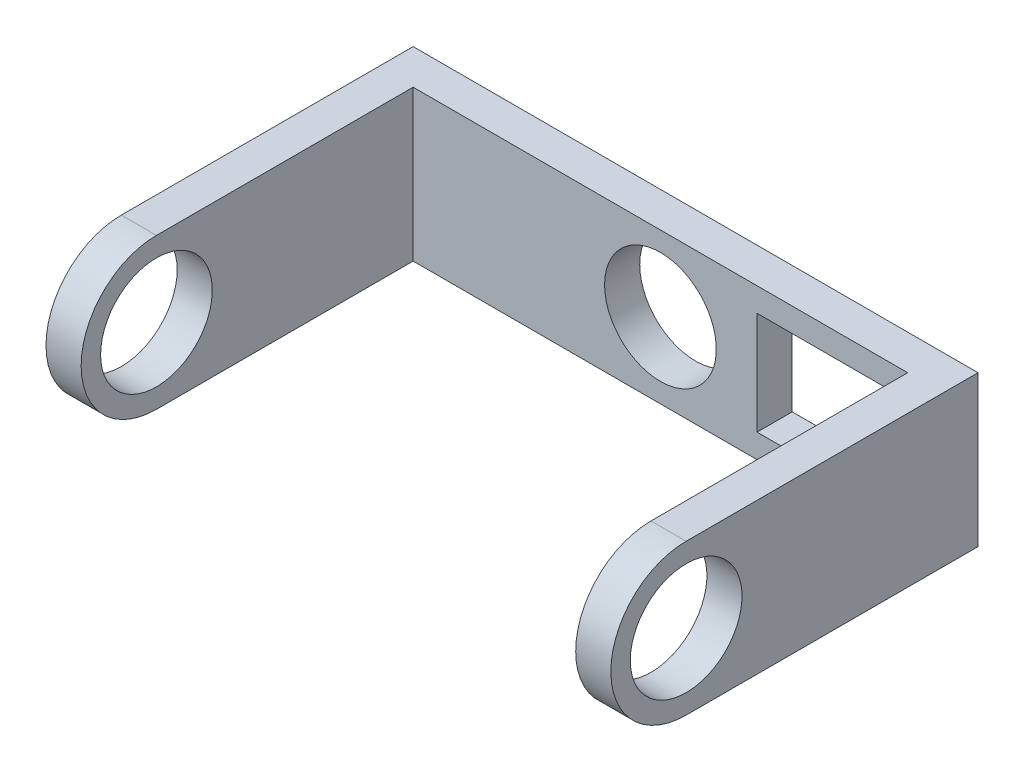
SolidWorks part; units mm, degrees
ref_plane "Front Plane" through (0, 0, 0) normal (0, 0, 1) x (1, 0, 0)
ref_plane "Top Plane" through (0, 0, 0) normal (0, 1, 0) x (1, 0, 0)
ref_plane "Right Plane" through (0, 0, 0) normal (1, 0, 0) x (0, 0, -1)
sketch "Sketch1" plane through (0, 0, 0) normal (0, 1, 0) x (1, 0, 0)
  line L0 (-56.25, 0) -> (56.25, 0) construction
  line L1 (-56.25, 11.125) -> (-56.25, -11.125)
  line L2 (-49.25, 11.125) -> (-49.25, -11.125)
  line L3 (-56.25, -11.125) -> (-49.25, -11.125)
  line L4 (-56.25, 11.125) -> (-49.25, 11.125)
  line L5 (0, 0) -> (0, 60) construction
  line L6 (56.25, 60) -> (-56.25, 60)
  line L7 (-56.25, 60) -> (-56.25, 11.125)
  line L8 (-49.25, 11.125) -> (-49.25, 53)
  line L9 (56.25, 11.125) -> (49.25, 11.125)
  line L10 (49.25, 11.125) -> (49.25, -11.125)
  line L11 (56.25, -11.125) -> (49.25, -11.125)
  line L12 (56.25, 11.125) -> (56.25, -11.125)
  line L13 (49.25, 11.125) -> (49.25, 53)
  line L14 (56.25, 60) -> (56.25, 11.125)
  line L15 (-49.25, 53) -> (49.25, 53)
  line L16 (-56.25, -11.125) -> (-56.25, -13.125)
  line L17 (-56.25, -13.125) -> (-49.25, -13.125)
  line L18 (-49.25, -13.125) -> (-49.25, -11.125)
  line L19 (49.25, -13.125) -> (49.25, -11.125)
  line L20 (56.25, -13.125) -> (49.25, -13.125)
  line L21 (56.25, -11.125) -> (56.25, -13.125)
  circle A0 centre (0, 0) radius 44.45 construction
  point P5 (0, 0)
  point P9 (-56.25, 0)
  point P15 (0, 60)
  dimension "D1" = 88.9
  dimension "D2" = 112.5
  dimension "D3" = 22.25
  dimension "D5" = 60
  dimension "D6" = 7
  dimension "D7" = 7
  dimension "D8" = 2
  dimension "D4" = 2
extrude "Boss-Extrude1" add sketch "Sketch1" along normal mid plane 30 contours L17 L18 L3 L16 | L4 L1 L3 L2 | L8 L15 L13 L9 L14 L6 L7 L4 | L12 L9 L10 L11 | L21 L11 L19 L20 region at (-52.75, 0, 0) region at (-55.0234, 0, -35.5625) region at (-52.75, 0, 12.125) region at (52.75, 0, 0) region at (52.75, 0, 12.125)
sketch "Sketch2" plane through (-56.25, 0, 0) normal (-1, 0, 0) x (0, 0, 1)
  line L0 (13.125, 15) -> (13.125, -15) construction
  line L1 (-60, 15) -> (13.125, 15) construction
  line L2 (-60, -15) -> (13.125, -15) construction
  line L3 (-1.875, 15) -> (13.125, 15)
  line L4 (13.125, 15) -> (13.125, -15)
  line L5 (13.125, -15) -> (-1.875, -15)
  circle A0 centre (-1.875, 0) radius 15
  circle A1 centre (-1.875, 0) radius 11.125
  line M1 (-60, -15) -> (13.125, -15)
  line M2 (13.125, -15) -> (13.125, 15)
  line M3 (13.125, 15) -> (-60, 15)
  dimension "D1" = 22.25
extrude "Cut-Extrude1" cut sketch "Sketch2" against normal through all both and the other way through all contours A1 | A0 L4 M3 | A0 M1 M2 region at (-56.25, 11.6495, 9.7745) region at (-56.25, -11.6495, 9.7745) region at (-56.25, 0, -1.875)
sketch "Sketch3" plane through (0, 0, -60) normal (0, 0, -1) x (-1, 0, 0)
  circle A0 centre (0, 0) radius 11.125
  dimension "D1" = 22.25
extrude "Cut-Extrude2" cut sketch "Sketch3" against normal up to surface (7 mm away) up to face at (0, 0, -53)
ref_plane "Plane1" through (49.25, 15, -53) normal (0, -1, 0) x (-1, 0, 0)
sketch "Sketch6" plane through (0, 0, -60) normal (0, 0, -1) x (-1, 0, 0)
  line L0 (-49.25, 15) -> (-49.25, -15) construction
  line L1 (-49.25, -10.25) -> (-19.25, -10.25)
  line L2 (-49.25, -10.25) -> (-49.25, 10.25)
  line L3 (-49.25, 10.25) -> (-19.25, 10.25)
  line L4 (-19.25, -10.25) -> (-19.25, 10.25)
  line L5 (-49.25, -10.25) -> (-19.25, 10.25) construction
  line L6 (-49.25, 10.25) -> (-19.25, -10.25) construction
  point P0 (-34.25, 0)
  dimension "D1" = 20.5
  dimension "D2" = 30
extrude "Cut-Extrude3" cut sketch "Sketch6" against normal up to surface (7 mm away) up to face at (-11.125, 0, -53)
